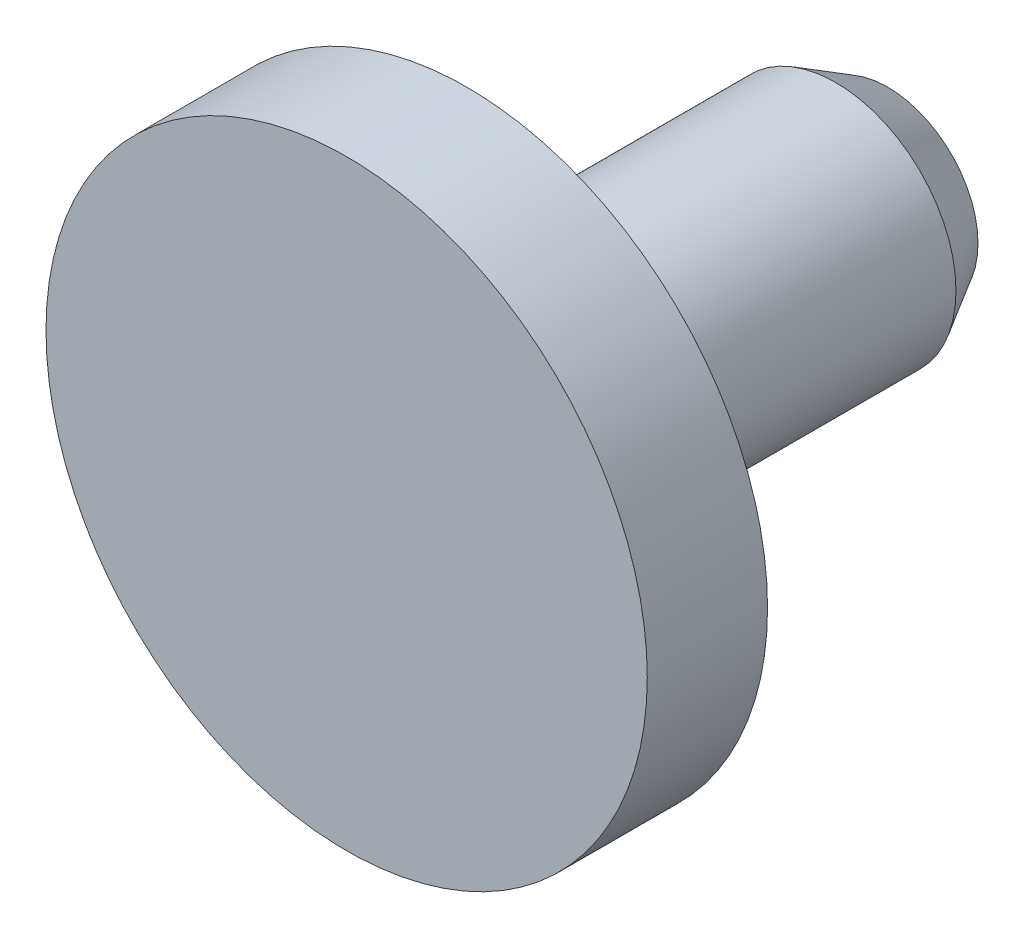
SolidWorks part; units mm, degrees
ref_plane "Alzado" through (0, 0, 0) normal (0, 0, 1) x (1, 0, 0)
ref_plane "Planta" through (0, 0, 0) normal (0, 1, 0) x (1, 0, 0)
ref_plane "Vista lateral" through (0, 0, 0) normal (1, 0, 0) x (0, 0, -1)
sketch "Croquis1" plane through (0, 0, 0) normal (0, 0, 1) x (1, 0, 0)
  circle A0 centre (0, 0) radius 5
  dimension "D1" = 10
extrude "Saliente-Extruir1" add sketch "Croquis1" along normal blind 2
sketch "Croquis2" plane through (0, 0, 0) normal (0, 0, 1) x (1, 0, 0)
  circle A0 centre (0, 0) radius 2
  dimension "D1" = 4
extrude "Saliente-Extruir2" add sketch "Croquis2" against normal blind 7
chamfer "Chaflán1" distance 0.5 angle 60 1 edges at (2, 0, -7) first distance on face at (2, 0, -7)
